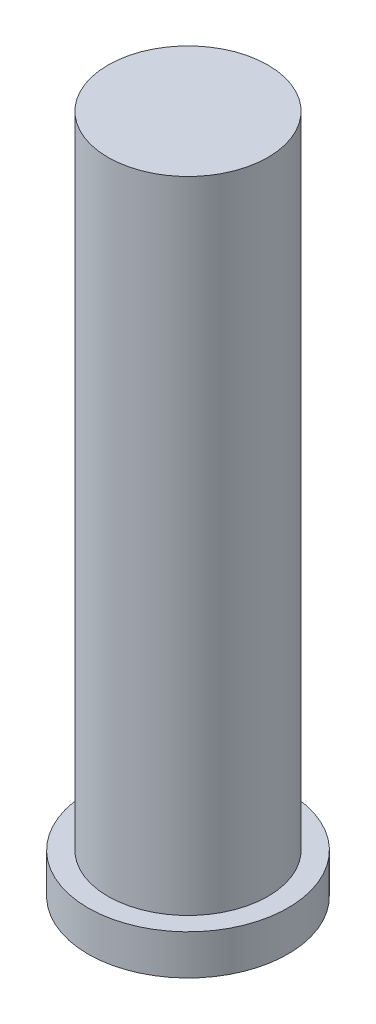
SolidWorks part; units mm, degrees
ref_plane "Front Plane" through (0, 0, 0) normal (0, 0, 1) x (1, 0, 0)
ref_plane "Top Plane" through (0, 0, 0) normal (0, 1, 0) x (1, 0, 0)
ref_plane "Right Plane" through (0, 0, 0) normal (1, 0, 0) x (0, 0, -1)
sketch "Sketch2" plane through (0, 0, 0) normal (0, 1, 0) x (1, 0, 0)
  circle A0 centre (0, 0) radius 1.25
  circle A1 centre (0, 0) radius 1
  dimension "D1" = 2
  dimension "D2" = 2.5
extrude "Boss-Extrude1" add sketch "Sketch2" along normal blind 8 contours A1
extrude "Boss-Extrude2" add sketch "Sketch2<3>" against normal blind 0.5 contours A0
sketch "Sketch2<3>" plane through (0, 0, 0) normal (0, 1, 0) x (1, 0, 0) same geometry as "Sketch2"
equation "\"pinDia\" = 2"
equation "\"headHeight\"= .5mm"
equation "\"headDia\" = 2.5"
equation "\"D1@Sketch2\"=\"pinDia\""
equation "\"D2@Sketch2\"=\"headDia\""
equation "\"pinLen\"= 8mm"
equation "\"D1@Boss-Extrude1\"=\"pinLen\""
equation "\"D1@Boss-Extrude2\"=\"headHeight\""
